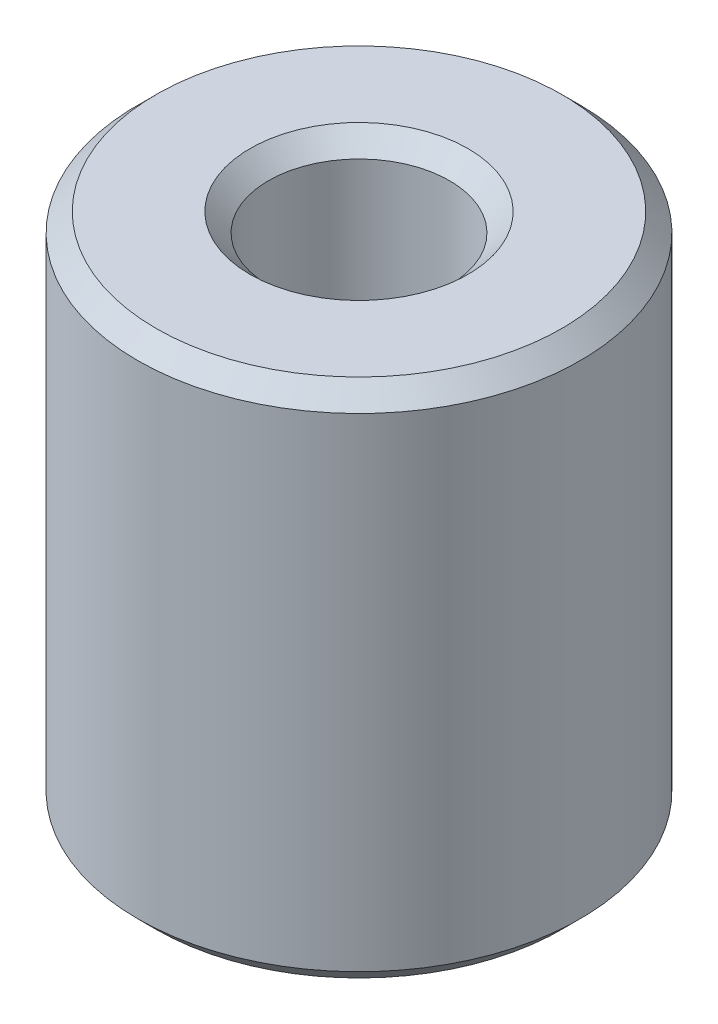
SolidWorks part; units mm, degrees
ref_plane "Front Plane" through (0, 0, 0) normal (0, 0, 1) x (1, 0, 0)
ref_plane "Top Plane" through (0, 0, 0) normal (0, 1, 0) x (1, 0, 0)
ref_plane "Right Plane" through (0, 0, 0) normal (1, 0, 0) x (0, 0, -1)
sketch "Sketch1" plane through (0, 0, 0) normal (0, 1, 0) x (1, 0, 0)
  circle A0 centre (0, 0) radius 37.5
  dimension "SLEEVE_OD" = 75
extrude "Boss-Extrude1" add sketch "Sketch1" along normal blind 88.2022
sketch "Sketch2" plane through (0, 0, 0) normal (0, 1, 0) x (1, 0, 0)
  circle A0 centre (0, 0) radius 15.3397
  dimension "BORE_D" = 30.6793
extrude "Cut-Extrude1" cut sketch "Sketch2" along normal through all
chamfer "Chamfer1" distance 3.1371 angle 45 4 edges at (0, 88.2022, 15.3397) (0, 0, 15.3397) (0, 0, 37.5) (0, 88.2022, 37.5)
